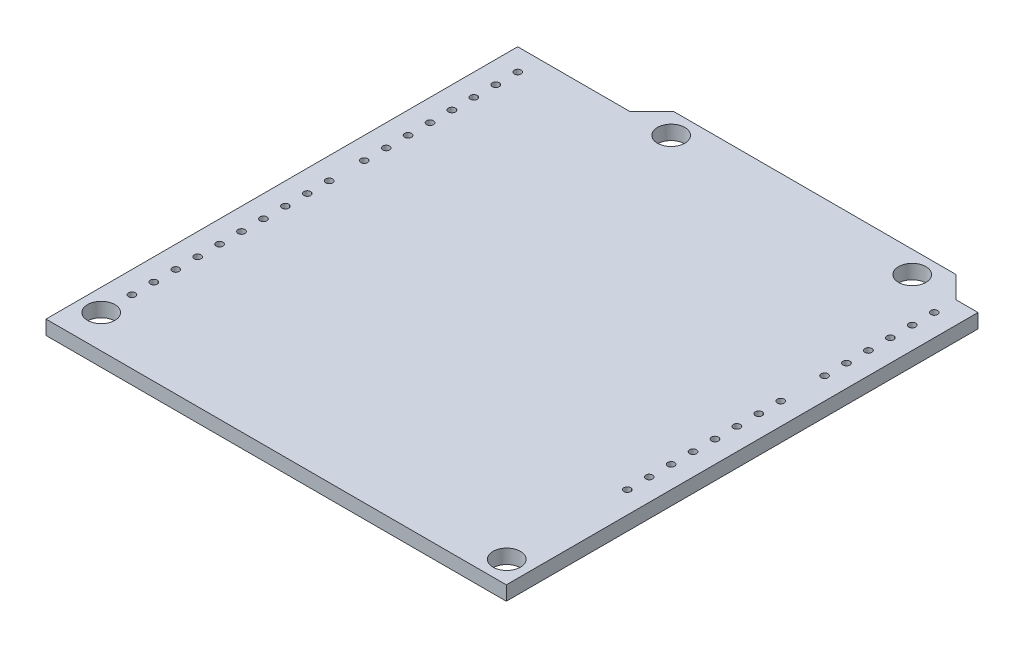
SolidWorks part; units mm, degrees
material "E-Glass Fiber"
ref_plane "Front Plane" through (0, 0, 0) normal (0, 0, 1) x (1, 0, 0)
ref_plane "Top Plane" through (0, 0, 0) normal (0, 1, 0) x (1, 0, 0)
ref_plane "Right Plane" through (0, 0, 0) normal (1, 0, 0) x (0, 0, -1)
sketch "Sketch1" plane through (0, 0, 0) normal (0, 1, 0) x (1, 0, 0)
  line L0 (-29.337, 0) -> (29.337, 0) construction
  line L1 (0, 0) -> (-53.34, 0)
  line L2 (0, 0) -> (0, 66.04)
  line L3 (-5.08, 68.58) -> (-37.846, 68.58)
  line L4 (-53.34, 0) -> (-53.34, 66.04)
  line L5 (-53.34, 66.04) -> (-40.386, 66.04)
  line L6 (-40.386, 66.04) -> (-37.846, 68.58)
  line L7 (-5.08, 68.58) -> (-2.54, 66.04)
  line L8 (-2.54, 66.04) -> (0, 66.04)
  circle A0 centre (-7.62, 66.04) radius 1.5875
  circle A1 centre (-35.56, 66.04) radius 1.5875
  circle A2 centre (-2.54, 13.97) radius 1.5875
  circle A3 centre (-50.8, 15.24) radius 1.5875
  dimension "D8" = 3.175
  dimension "D1" = 68.58
  dimension "D2" = 53.34
  dimension "D3" = 66.04
  dimension "D4" = 2.54
  dimension "D5" = 45
  dimension "D6" = 45
  dimension "D7" = 40.386
  dimension "D9" = 66.04
  dimension "D10" = 35.56
  dimension "D11" = 7.62
  dimension "D12" = 13.97
  dimension "D13" = 2.54
  dimension "D14" = 15.24
  dimension "D15" = 50.8
extrude "Boss-Extrude1" add sketch "Sketch1" against normal blind 1.65
sketch "Sketch2" plane through (0, 0, 0) normal (0, 1, 0) x (1, 0, 0)
  line L0 (0, -0.9075) -> (0, 0.9075) construction
  line L1 (-0.9075, 0) -> (0.9075, 0) construction
  circle A0 centre (-2.54, 27.94) radius 0.4
  dimension "D1" = 0.8
  dimension "D2" = 2.54
  dimension "D3" = 27.94
extrude "Cut-Extrude1" cut sketch "Sketch2" against normal blind 1.65
sketch "Sketch3" plane through (0, 0, 0) normal (0, 1, 0) x (1, 0, 0)
  line L0 (0, -0.9075) -> (0, 0.9075) construction
  line L1 (-0.9075, 0) -> (0.9075, 0) construction
  circle A0 centre (-50.8, 18.796) radius 0.4
  dimension "D2" = 0.8
  dimension "D1" = 50.8
  dimension "D3" = 18.796
extrude "Cut-Extrude2" cut sketch "Sketch3" against normal blind 1.65
pattern_linear "LPattern1" count 15 spacing 2.54 along (0, 0, -1) skipping (8, 0) of "Cut-Extrude1"
sketch "Sketch4" plane through (0, 0, 0) normal (0, 1, 0) x (1, 0, 0)
  line L0 (-0.9075, 0) -> (0.9075, 0) construction
  line L1 (0, -0.9075) -> (0, 0.9075) construction
  circle A0 centre (-50.8, 45.72) radius 0.4
  dimension "D3" = 0.8
  dimension "D1" = 45.72
  dimension "D2" = 50.8
extrude "Cut-Extrude3" cut sketch "Sketch4" against normal blind 1.65
pattern_linear "LPattern2" count 10 spacing 2.54 along (0, 0, -1) of "Cut-Extrude2"
pattern_linear "LPattern3" count 8 spacing 2.54 along (0, 0, -1) of "Cut-Extrude3"
sketch "Sketch5" plane through (0, 0, 0) normal (0, 1, 0) x (1, 0, 0)
  line L0 (-27.89, 66.18) -> (-27.89, 63.64) construction
  line L1 (-30.43, 66.18) -> (-25.35, 66.18) construction
  line L2 (-30.43, 66.18) -> (-30.43, 63.64) construction
  line L3 (-30.43, 63.64) -> (-25.35, 63.64) construction
  line L4 (-25.35, 66.18) -> (-25.35, 63.64) construction
  line L5 (-0.9075, 0) -> (0.9075, 0) construction
  line L6 (0, -0.9075) -> (0, 0.9075) construction
  circle A0 centre (-30.43, 66.18) radius 0.4
  circle A1 centre (-27.89, 66.18) radius 0.4
  circle A2 centre (-25.35, 66.18) radius 0.4
  circle A3 centre (-25.35, 63.64) radius 0.4
  circle A4 centre (-27.89, 63.64) radius 0.4
  circle A5 centre (-30.43, 63.64) radius 0.4
  circle A6 centre (-47.498, 15.748) radius 0.4
  circle A7 centre (-47.498, 18.288) radius 0.4
  circle A8 centre (-47.498, 20.828) radius 0.4
  circle A9 centre (-44.958, 20.828) radius 0.4
  circle A10 centre (-44.958, 18.288) radius 0.4
  circle A11 centre (-44.958, 15.748) radius 0.4
  circle A12 centre (-42.418, 18.288) radius 0.4
  circle A13 centre (-42.418, 20.828) radius 0.4
  circle A14 centre (-39.878, 20.828) radius 0.4
  circle A15 centre (-39.878, 18.288) radius 0.4
  circle A16 centre (-26.162, 21.463) radius 0.5
  circle A17 centre (-26.162, 16.383) radius 0.5
  dimension "D4" = 0.8
  dimension "D14" = 1
  dimension "D1" = 2.54
  dimension "D2" = 2.54
  dimension "D3" = 2.54
  dimension "D5" = 63.64
  dimension "D6" = 30.43
  dimension "D7" = 2.54
  dimension "D8" = 2.54
  dimension "D9" = 2.54
  dimension "D10" = 2.54
  dimension "D11" = 2.54
  dimension "D12" = 47.498
  dimension "D13" = 15.748
  dimension "D15" = 5.08
  dimension "D16" = 16.383
  dimension "D17" = 26.162
extrude "Cut-Extrude4" [suppressed] cut sketch "Sketch5" against normal blind 10
sketch "Sketch6" plane through (0, 0, 0) normal (0, 1, 0) x (1, 0, 0)
  line L0 (0, -0.9075) -> (0, 0.9075) construction
  line L1 (-0.9075, 0) -> (0.9075, 0) construction
  line L2 (-20.193, 29.845) -> (-20.193, 32.385) construction
  circle A0 centre (-20.193, 29.845) radius 0.4
  circle A1 centre (-12.573, 29.845) radius 0.4
  circle A2 centre (-20.193, 32.385) radius 0.4
  circle A3 centre (-12.573, 32.385) radius 0.4
  circle A4 centre (-20.193, 34.925) radius 0.4
  circle A5 centre (-12.573, 34.925) radius 0.4
  circle A6 centre (-20.193, 37.465) radius 0.4
  circle A7 centre (-12.573, 37.465) radius 0.4
  circle A8 centre (-20.193, 40.005) radius 0.4
  circle A9 centre (-12.573, 40.005) radius 0.4
  circle A10 centre (-20.193, 42.545) radius 0.4
  circle A11 centre (-12.573, 42.545) radius 0.4
  circle A12 centre (-20.193, 45.085) radius 0.4
  circle A13 centre (-12.573, 45.085) radius 0.4
  circle A14 centre (-20.193, 47.625) radius 0.4
  circle A15 centre (-12.573, 47.625) radius 0.4
  circle A16 centre (-20.193, 50.165) radius 0.4
  circle A17 centre (-12.573, 50.165) radius 0.4
  circle A18 centre (-20.193, 52.705) radius 0.4
  circle A19 centre (-12.573, 52.705) radius 0.4
  circle A20 centre (-20.193, 55.245) radius 0.4
  circle A21 centre (-12.573, 55.245) radius 0.4
  circle A22 centre (-20.193, 57.785) radius 0.4
  circle A23 centre (-12.573, 57.785) radius 0.4
  circle A24 centre (-20.193, 60.325) radius 0.4
  circle A25 centre (-12.573, 60.325) radius 0.4
  circle A26 centre (-20.193, 62.865) radius 0.4
  circle A27 centre (-12.573, 62.865) radius 0.4
  dimension "D1" = 0.8
  dimension "D2" = 7.62
  dimension "D3" = 12.573
  dimension "D4" = 29.845
  dimension "D6" = 2.54
  dimension "D5" = 14
extrude "Cut-Extrude5" [suppressed] cut sketch "Sketch6" against normal blind 10
sketch "Croquis1" plane through (0, 0, 0) normal (0, 1, 0) x (1, 0, 0)
  line L0 (-53.34, 66.04) -> (-53.34, 0) construction
  line L1 (-53.34, 0) -> (0, 0)
  line L2 (-53.34, 0) -> (-53.34, 11.38)
  line L3 (-53.34, 11.38) -> (0, 11.38)
  line L4 (0, 0) -> (0, 11.38)
  line L5 (-5.08, 68.58) -> (-37.846, 68.58) construction
  dimension "D1" = 57.2
extrude "Cortar-Extruir1" cut sketch "Croquis1" against normal up to surface (1.65 mm away) up to face at (-50.8, -1.65, -47.86)
equation "\"D13@Sketch5\"=0.001*25.4*620"
equation "\"D16@Sketch5\"=645*0.001*25.4"
